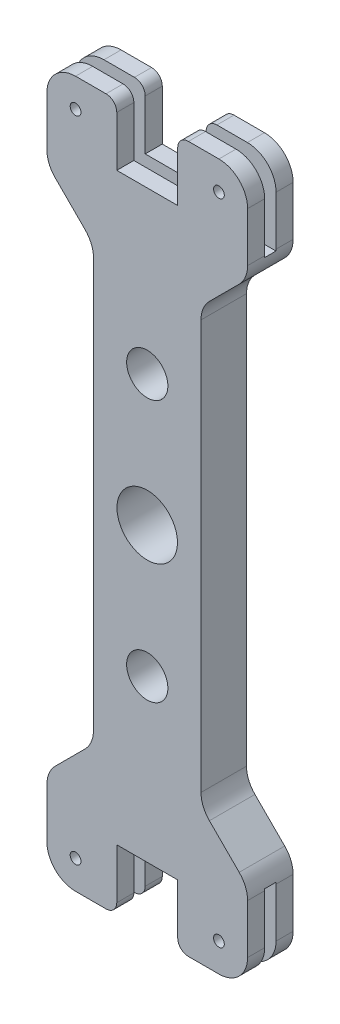
SolidWorks part; units mm, degrees
ref_plane "Front Plane" through (0, 0, 0) normal (0, 0, 1) x (1, 0, 0)
ref_plane "Top Plane" through (0, 0, 0) normal (0, 1, 0) x (1, 0, 0)
ref_plane "Right Plane" through (0, 0, 0) normal (1, 0, 0) x (0, 0, -1)
sketch "Sketch1" plane through (0, 0, 0) normal (0, 0, 1) x (1, 0, 0)
  line L1 (0, -5.2388) -> (0, 5.2388) construction
  line L2 (5.2388, 0) -> (-5.2388, 0) construction
  line L3 (-28, 73.3978) -> (-28, 90.475)
  line L4 (-20, 98.475) -> (-11.5, 98.475)
  line L5 (28, 90.475) -> (28, 73.3978)
  line L6 (28, 73.3978) -> (15, 60.3978)
  line L7 (15, 60.3978) -> (15, -60.3978)
  line L13 (-15, -60.3978) -> (-15, 60.3978)
  line L14 (-15, 60.3978) -> (-28, 73.3978)
  line L15 (0, -1000) -> (0, 49000) construction
  line L16 (-1000, 0) -> (49000, 0) construction
  line L17 (-8.5, 95.475) -> (-8.5, 81.475)
  line L18 (-8.5, 81.475) -> (8.5, 81.475)
  line L19 (8.5, 81.475) -> (8.5, 95.475)
  line L20 (11.5, 98.475) -> (20, 98.475)
  line L21 (-20, 98.475) -> (-20, 90.475) construction
  line L22 (-20, 90.475) -> (-28, 90.475) construction
  line L23 (-8.5, 81.475) -> (-22.2886, 67.6864) construction
  line L24 (-8.5, 81.475) -> (-28, 81.475) construction
  line L25 (28, -73.3978) -> (15, -60.3978)
  line L26 (28, -90.475) -> (28, -73.3978)
  line L27 (11.5, -98.475) -> (20, -98.475)
  line L28 (8.5, -81.475) -> (8.5, -95.475)
  line L29 (-8.5, -81.475) -> (8.5, -81.475)
  line L30 (-8.5, -95.475) -> (-8.5, -81.475)
  line L31 (-20, -98.475) -> (-11.5, -98.475)
  line L32 (-28, -73.3978) -> (-28, -90.475)
  line L33 (-15, -60.3978) -> (-28, -73.3978)
  circle A0 centre (0, 0) radius 8.4375
  circle A1 centre (-20, 90.475) radius 1.5
  circle A3 centre (20, 90.475) radius 1.5
  circle A4 centre (20, -90.475) radius 1.5
  circle A5 centre (-20, -90.475) radius 1.5
  arc A6 (-28, 90.475) -> (-20, 98.475) centre (-20, 90.475) cw
  arc A7 (20, 98.475) -> (28, 90.475) centre (20, 90.475) cw
  arc A8 (20, -98.475) -> (28, -90.475) centre (20, -90.475) ccw
  arc A9 (-28, -90.475) -> (-20, -98.475) centre (-20, -90.475) ccw
  arc A10 (-8.5, -95.475) -> (-11.5, -98.475) centre (-11.5, -95.475) cw
  arc A11 (11.5, -98.475) -> (8.5, -95.475) centre (11.5, -95.475) cw
  arc A12 (8.5, 95.475) -> (11.5, 98.475) centre (11.5, 95.475) cw
  arc A13 (-8.5, 95.475) -> (-11.5, 98.475) centre (-11.5, 95.475) ccw
  point P22 (0, 81.475)
  point P39 (15, 0)
  point P51 (-15, 0)
  point P53 (-8.5, -98.475)
  point P56 (8.5, -98.475)
  point P59 (8.5, 98.475)
  point P62 (-8.5, 98.475)
  dimension "D1" = 16.875
  dimension "D9" = 3
  dimension "D3" = 30
  dimension "D4" = 17
  dimension "D5" = 40
  dimension "D6" = 8
  dimension "D7" = 180.95
  dimension "D8" = 45
  dimension "D10" = 17
extrude "Boss-Extrude1" add sketch "Sketch1" along normal mid plane 12.7
fillet "Fillet1" radius 8 8 edges at (-28, 73.3978, 0) (-15, 60.3978, 0) (-28, -73.3978, 0) (-15, -60.3978, 0) (15, -60.3978, 0) (28, -73.3978, 0) (28, 73.3978, 0) (15, 60.3978, 0)
sketch "Sketch3" plane through (0, 98.475, 0) normal (0, 1, 0) x (1, 0, 0)
  line L0 (-28, -6.35) -> (-28, 6.35) construction
  line L1 (28, 1.5875) -> (-28, 1.5875)
  line L2 (28, 1.5875) -> (28, -1.5875)
  line L3 (28, -1.5875) -> (-28, -1.5875)
  line L4 (-28, 1.5875) -> (-28, -1.5875)
  line L5 (28, 1.5875) -> (-28, -1.5875) construction
  line L6 (28, -1.5875) -> (-28, 1.5875) construction
  point P0 (0, 0)
  dimension "D1" = 3.175
extrude "Cut-Extrude1" cut sketch "Sketch3" against normal blind 22.22
mirror "Mirror1" about plane through (0, 0, 0) normal (0, 1, 0) of "Cut-Extrude1"
sketch "Sketch4" plane through (0, 0, 6.35) normal (0, 0, 1) x (1, 0, 0)
  line L0 (0, 36.5125) -> (0, -36.5125) construction
  point P0 (0, 36.5125)
  point P2 (0, -36.5125)
  point P4 (0, 0)
  dimension "D2" = 73.025
hole_wizard "7/16 Clearance Hole4" positions "Sketch4" profile "Sketch5" hole size "7/16" standard "ANSI Inch" end condition through all
sketch "Sketch5" plane through (0, 36.5125, 6.35) normal (1, 0, 0) x (0, -1, 0)
  line L0 (0, 0) -> (0, 12.7)
  line L1 (0, 12.7) -> (5.7544, 12.7)
  line L2 (5.7544, 12.7) -> (5.7544, 0)
  line L5 (5.7544, 0) -> (0, 0)
  line L11 (0, -6.35) -> (0, 107.95) construction
  dimension "Thru Hole Dia." = 11.5087
  dimension "Thru Hole Depth" = 12.7
equation "\"D1@Fillet1\"=\"D6@Sketch1\""
equation "\"Shaft Size\"= 5in / 8"
equation "\"Bearing Screw Spacing\"= 2.875in"
equation "\"D1@Sketch1\"= \"Shaft Size\" + 1mm"
equation "\"D2@Sketch4\"= \"Bearing Screw Spacing\""
equation "\"Plate Thickness\"= 1in / 2"
equation "\"D1@Boss-Extrude1\"=\"Plate Thickness\""
